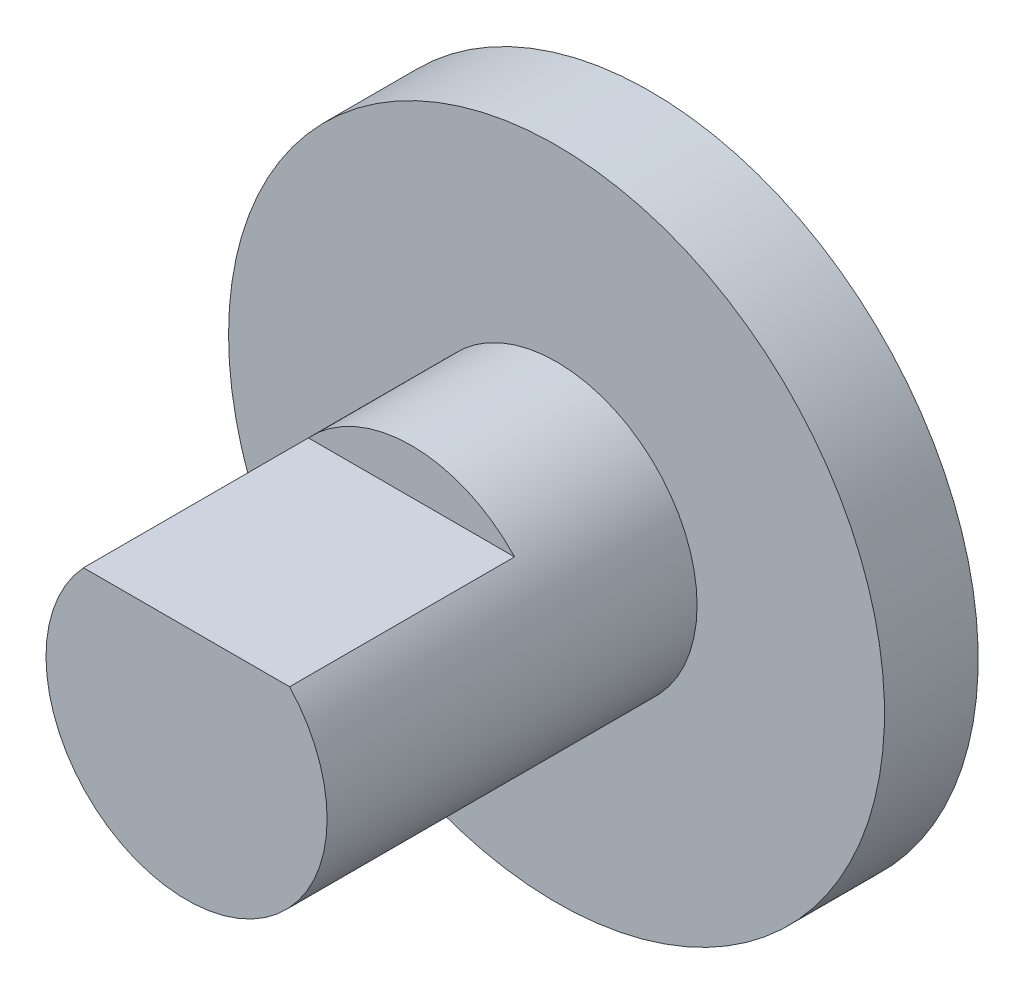
SolidWorks part; units mm, degrees
ref_plane "Front Plane" through (0, 0, 0) normal (0, 0, 1) x (1, 0, 0)
ref_plane "Top Plane" through (0, 0, 0) normal (0, 1, 0) x (1, 0, 0)
ref_plane "Right Plane" through (0, 0, 0) normal (1, 0, 0) x (0, 0, -1)
sketch "Sketch1" plane through (0, 0, 0) normal (0, 0, 1) x (1, 0, 0)
  circle A0 centre (0, 0) radius 7.5
  dimension "D1" = 15
extrude "Boss-Extrude1" add sketch "Sketch1" along normal blind 19.74
sketch "Sketch2" plane through (0, 0, 0) normal (0, 0, -1) x (-1, 0, 0)
  circle A0 centre (0, 0) radius 17.5
  dimension "D1" = 35
extrude "Boss-Extrude2" add sketch "Sketch2" along normal blind 5
sketch "Sketch3" plane through (0, 0, 19.74) normal (0, 0, 1) x (1, 0, 0)
  line L0 (5.5268, 5.07) -> (5.4991, 5.1)
  line L1 (5.4991, 5.1) -> (-5.4991, 5.1)
  arc A0 (5.5268, 5.07) -> (-5.4991, 5.1) centre (0, 0) ccw
  dimension "D2" = 15
  dimension "D1" = 5.1
extrude "Cut-Extrude1" cut sketch "Sketch3" against normal blind 12 contours L1 A0 region at (0, 6.0745, 19.74)
